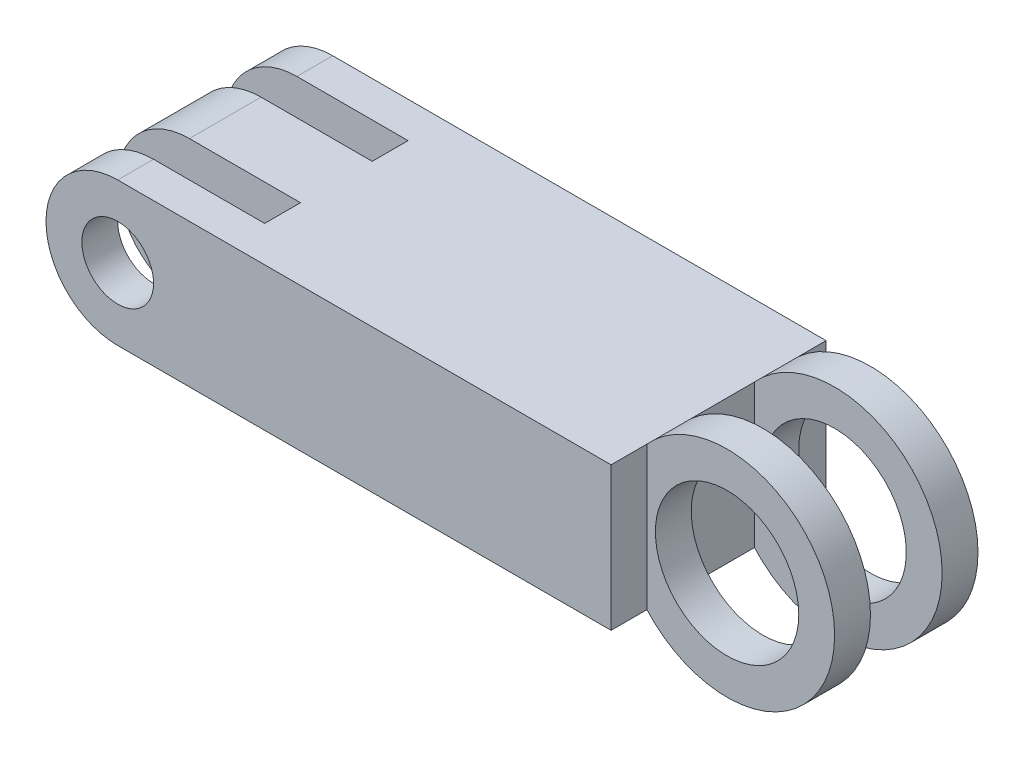
SolidWorks part; units mm, degrees
ref_plane "Front Plane" through (0, 0, 0) normal (0, 0, 1) x (1, 0, 0)
ref_plane "Top Plane" through (0, 0, 0) normal (0, 1, 0) x (1, 0, 0)
ref_plane "Right Plane" through (0, 0, 0) normal (1, 0, 0) x (0, 0, -1)
sketch "Sketch1" plane through (0, 0, 0) normal (0, 0, 1) x (1, 0, 0)
  line L0 (0, 12.7) -> (87.401, 12.7)
  line L2 (87.401, -12.7) -> (0, -12.7)
  line L3 (87.401, 12.7) -> (87.401, -12.7)
  arc A0 (0, 12.7) -> (0, -12.7) centre (0, 0) ccw
  circle A3 centre (101.6, 0) radius 19.05 construction
  dimension "D1" = 25.4
  dimension "D3" = 101.6
  dimension "D2" = 38.1
extrude "Boss-Extrude1" add sketch "Sketch1" along normal blind 38.1 contours A0 L2 L3 L0
ref_plane "Plane1" through (0, 0, 19.05) normal (0, 0, -1) x (-1, 0, 0)
sketch "Sketch2" plane through (0, 0, 0) normal (0, 0, 1) x (1, 0, 0)
  line L0 (0, -19.685) -> (19.685, -19.685)
  line L1 (19.685, -19.685) -> (19.685, 19.685)
  line L2 (19.685, 19.685) -> (0, 19.685)
  arc A0 (0, 19.685) -> (0, -19.685) centre (0, 0) ccw
  arc A1 (0, 12.7) -> (0, -12.7) centre (0, 0) ccw construction
  dimension "D1" = 39.37
extrude "Cut-Extrude1" cut sketch "Sketch2" along normal blind 6.35 from offset 6.35
mirror "Mirror1" about plane through (0, 0, 19.05) normal (0, 0, -1) of "Cut-Extrude1"
sketch "Sketch3" plane through (0, 0, 38.1) normal (0, 0, 1) x (1, 0, 0)
  circle A0 centre (0, 0) radius 6.35
  arc A1 (0, 12.7) -> (0, -12.7) centre (0, 0) ccw construction
  dimension "D1" = 12.7
extrude "Cut-Extrude2" cut sketch "Sketch3" against normal through all both and the other way through all contours A0
ref_axis "Axis1" through (0, 0, 0.2431) along (0, 0, 1)
sketch "Sketch6" plane through (0, 0, 19.05) normal (0, 0, -1) x (-1, 0, 0)
  circle A0 centre (-101.6, 0) radius 19.05
  point P2 (-101.2232, 8.7416)
  point P4 (0, 0)
  dimension "D1" = 38.1
  dimension "D2" = 101.6
extrude "Boss-Extrude2" add sketch "Sketch6" along normal blind 6.35 from offset 6.35
sketch "Sketch7" plane through (0, 0, 6.35) normal (0, 0, -1) x (-1, 0, 0)
  circle A0 centre (-101.6, 0) radius 12.7
  dimension "D1" = 25.4
extrude "Cut-Extrude5" cut sketch "Sketch7" against normal through all both and the other way through all
mirror "Mirror3" about plane through (0, 0, 19.05) normal (0, 0, -1) of "Cut-Extrude5", "Boss-Extrude2"
ref_axis "Axis2" through (101.6, 0, 37.7537) along (0, 0, -1)
